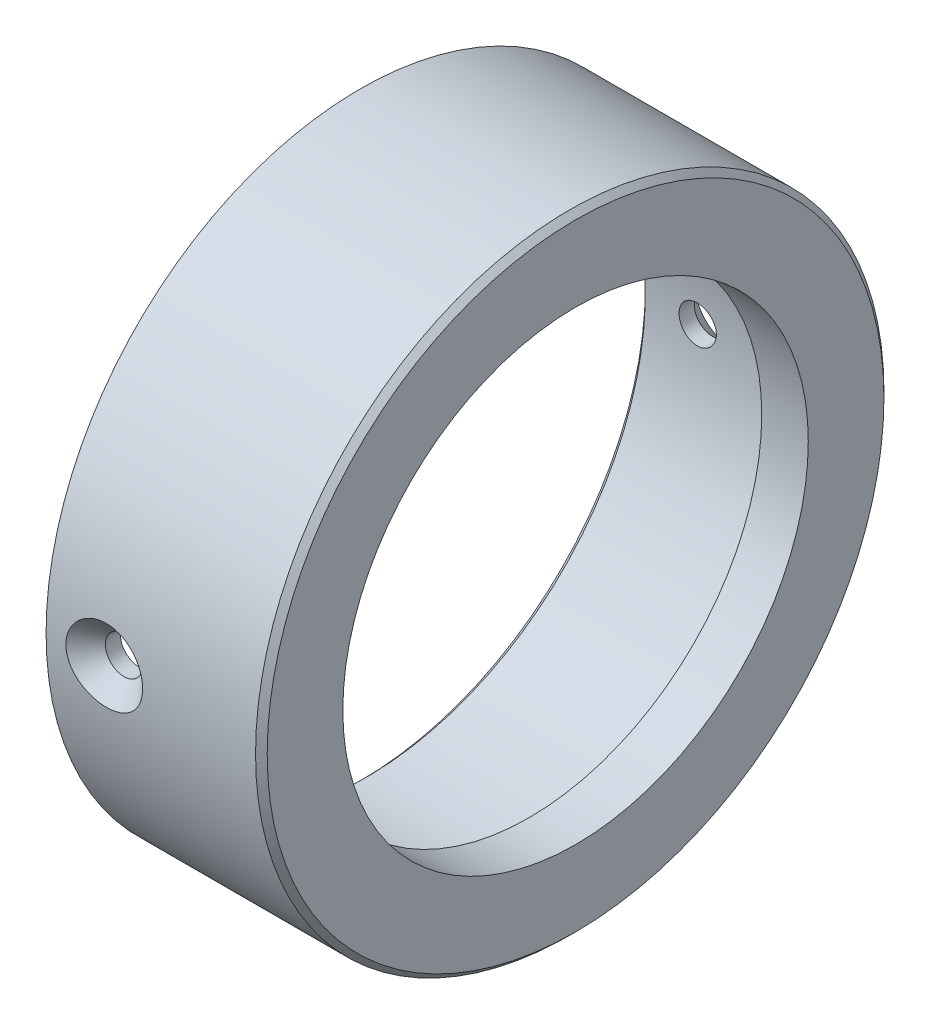
SolidWorks part; units mm, degrees
ref_plane "Přední rovina" through (0, 0, 0) normal (0, 0, 1) x (1, 0, 0)
ref_plane "Horní rovina" through (0, 0, 0) normal (0, 1, 0) x (1, 0, 0)
ref_plane "Pravá rovina" through (0, 0, 0) normal (1, 0, 0) x (0, 0, -1)
sketch "Skica1" plane through (0, 0, 0) normal (0, 0, 1) x (1, 0, 0)
  line L0 (-342.05, 21.5) -> (-342.05, -21.5) construction
  line L1 (-342.05, 21.5) -> (-342.05, -21.5) construction
  line L2 (-350.05, -20) -> (-344.05, -20) construction
  line L3 (-350.05, -20) -> (-344.05, -20) construction
  line L4 (-346.05, -20) -> (-342.05, -20)
  line L6 (-342.05, -20) -> (-342.05, -27)
  line L7 (-342.05, -27) -> (-360.55, -27)
  line L8 (-360.55, -27) -> (-360.55, -24)
  line L9 (-360.55, -24) -> (-346.05, -24)
  line L10 (-346.05, -24) -> (-346.05, -20)
  line L12 (-506.9511, 0) -> (94.0461, 0) construction
  line L13 (-365.55, -21) -> (-365.55, 21) construction
  line L14 (-390.1185, 0) -> (-358.6078, 0) construction
  dimension "D1" = 20
  dimension "D2" = 4
  dimension "D3" = 5
  dimension "D4" = 4
  dimension "D5" = 3
revolve "Rotovat1" add sketch "Skica1" angle 360 about L14
chamfer "Zkosení1" distance 0.5 angle 45 2 edges at (-342.05, 0, 27) (-360.55, 0, 24)
chamfer "Zkosení2" distance 0.5 angle 45 1 edges at (-346.05, 0, 24)
ref_plane "Rovina1" through (0, 0, -27) normal (0, 0, -1) x (-1, 0, 0)
sketch "Skica4" plane through (0, 0, -27) normal (0, 0, -1) x (-1, 0, 0)
  point P0 (355.55, 0)
hole_wizard "Kuželové zahloubení pro M3 šroubu se zápustnou hlavou plochou1" positions "3DSkica3" profile "Skica3" countersink size "M3" standard "ISO" end condition up to next
sketch3d "3DSkica3"
  point P0 (-355.55, 0, -27)
  point P10 (0, 0, 0)
sketch "Skica3" plane through (-355.55, 0, -27) normal (1, 0, 0) x (0, 1, 0)
  line L0 (0, 0) -> (0, 54)
  line L1 (0, 54) -> (1.6, 54)
  line L2 (1.6, 54) -> (1.6, 1.7)
  line L3 (1.6, 1.7) -> (3.3, 0)
  line L5 (3.3, 0) -> (0, 0)
  line L6 (-1.6, 1.7) -> (-3.3, 0) construction
  line L11 (0, -6.35) -> (0, 107.95) construction
  dimension "Průměr díry skrz" = 3.2
  dimension "Hloubka díry skrz" = 54
  dimension "Průměr blíz. kuž. zahloubení" = 6.6
  dimension "Úhel blíz. kuž. zahloubení" = 90
pattern_circular "Kruhové pole1" count 2 every 180 of "Kuželové zahloubení pro M3 šroubu se zápustnou hlavou plochou1"
